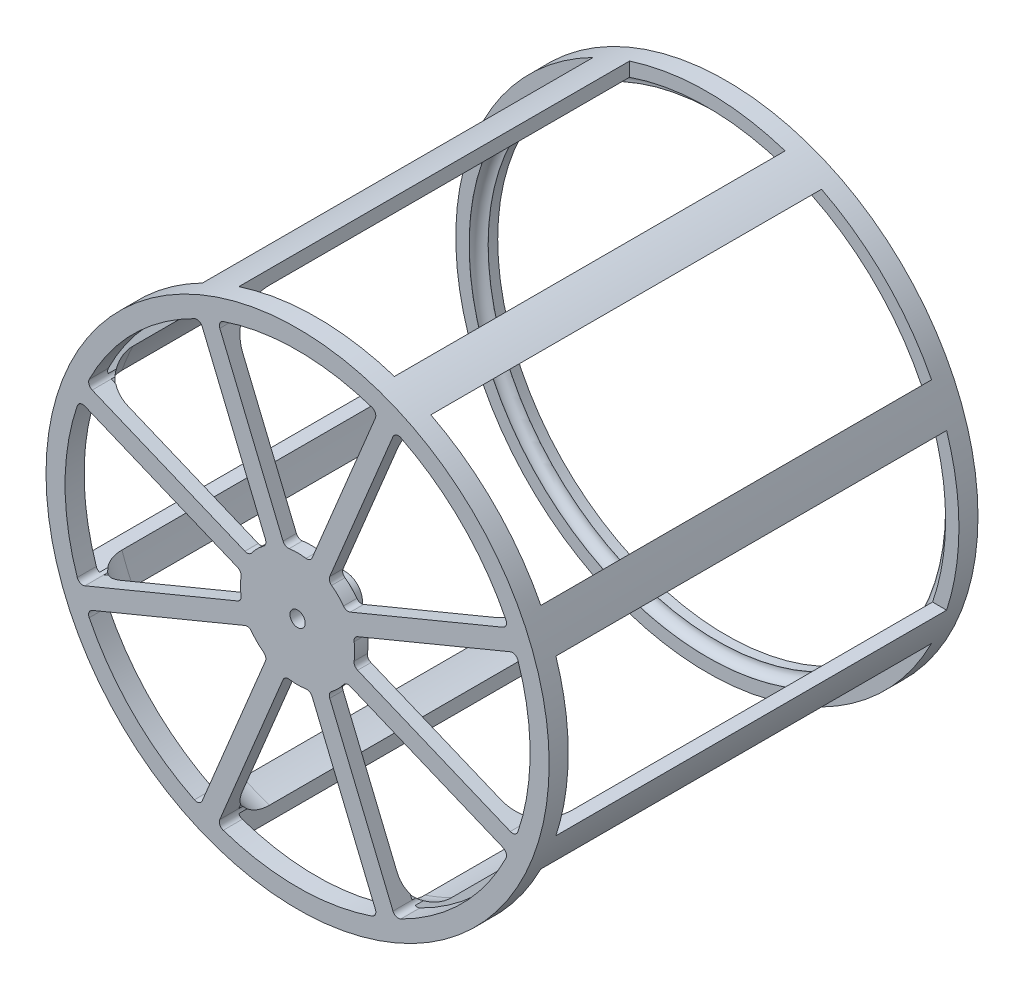
SolidWorks part; units mm, degrees
ref_plane "Front Plane" through (0, 0, 0) normal (0, 0, 1) x (1, 0, 0)
ref_plane "Top Plane" through (0, 0, 0) normal (0, 1, 0) x (1, 0, 0)
ref_plane "Right Plane" through (0, 0, 0) normal (1, 0, 0) x (0, 0, -1)
sketch "Sketch1" plane through (0, 0, 0) normal (1, 0, 0) x (0, 0, -1)
  line L0 (0, 0) -> (46.6464, 0) construction
  line L1 (1.778, 6.096) -> (1.778, 26.924)
  line L2 (57.15, 33.528) -> (0, 33.528)
  line L3 (0, 1.016) -> (0, 33.528)
  line L4 (54.6354, 31.75) -> (6.604, 31.75)
  line L5 (0, 1.016) -> (6.35, 1.016)
  line L6 (6.35, 1.016) -> (6.35, 2.286)
  line L7 (6.35, 2.286) -> (5.588, 2.286)
  line L8 (57.15, 33.528) -> (57.15, 30.48)
  line L9 (0, 3.7177) -> (0, 33.528) construction
  line L10 (0, 3.7177) -> (-5.2526, 1.8207) construction
  line L11 (57.15, 31.75) -> (1.778, 31.75) construction
  line L12 (1.778, 2.4695) -> (1.778, 31.75) construction
  line L13 (55.88, 30.5054) -> (55.88, 30.48)
  line L14 (1.778, 2.4695) -> (-4.6486, 0.1484) construction
  line L15 (55.88, 30.48) -> (57.15, 30.48)
  arc A0 (1.778, 6.096) -> (5.588, 2.286) centre (5.588, 6.096) ccw
  arc A1 (6.604, 31.75) -> (1.778, 26.924) centre (6.604, 26.924) ccw
  arc A2 (54.6354, 31.75) -> (55.88, 30.5054) centre (54.6354, 30.5054) cw
  point P25 (55.88, 31.75)
  dimension "D5" = 1.27
  dimension "D6" = 4.826
  dimension "D8" = 3.81
  dimension "D11" = 1.2446
  dimension "D1" = 2.032
  dimension "D2" = 63.5
  dimension "D3" = 1.778
  dimension "D4" = 6.35
  dimension "D7" = 57.15
  dimension "D9" = 1.27
  dimension "D10" = 1.27
revolve "Revolve1" add sketch "Sketch1" angle 360 about L0
sketch "Sketch3" plane through (0, 0, 0) normal (0, 0, 1) x (1, 0, 0)
  line L0 (0, 0) -> (14.7444, 35.5961) construction
  line L1 (0, 0) -> (-14.9584, 36.1127) construction
  line L2 (0, 0) -> (0, 50.266) construction
  line L3 (1.9386, 7.999) -> (10.3675, 28.348)
  line L4 (-1.9386, 7.999) -> (-10.3675, 28.348)
  arc A0 (-1.1224, 7.5369) -> (1.1224, 7.5369) centre (0, 0) cw
  arc A1 (-9.9071, 29.3616) -> (9.9071, 29.3616) centre (0, 0) cw
  circle A2 centre (0, 0) radius 33.528 construction
  arc A3 (10.3675, 28.348) -> (9.9071, 29.3616) centre (9.6635, 28.6396) ccw
  arc A4 (-9.9071, 29.3616) -> (-10.3675, 28.348) centre (-9.6635, 28.6396) ccw
  arc A5 (1.9386, 7.999) -> (1.1224, 7.5369) centre (1.2346, 8.2906) cw
  arc A6 (-1.9386, 7.999) -> (-1.1224, 7.5369) centre (-1.2346, 8.2906) ccw
  dimension "D3" = 2.54
  dimension "D4" = 7.62
  dimension "D5" = 2.54
  dimension "D6" = 0.762
  dimension "D1" = 22.5
  dimension "D2" = 45
extrude "Spoke" cut sketch "Sketch3" against normal blind 7.62
sketch "Sketch4" plane through (0, 0, 0) normal (0, 1, 0) x (1, 0, 0)
  line L0 (33.528, 57.15) -> (-33.528, 57.15) construction
  line L1 (-10.3675, 2.54) -> (10.3675, 2.54)
  line L2 (-10.3675, 2.54) -> (-10.3675, 54.61)
  line L3 (-10.3675, 54.61) -> (10.3675, 54.61)
  line L4 (10.3675, 2.54) -> (10.3675, 54.61)
  line L5 (-10.3675, 2.54) -> (10.3675, 54.61) construction
  line L6 (-10.3675, 54.61) -> (10.3675, 2.54) construction
  point P4 (0, 28.575)
  dimension "D1" = 2.54
  dimension "D2" = 2.54
extrude "Tread" cut sketch "Sketch4" along normal through all from offset 15.24
pattern_circular "CirPattern1" count 8 over 360 about axis through (0, 0, 0) along (0, 0, 1) of "Tread", "Spoke"
